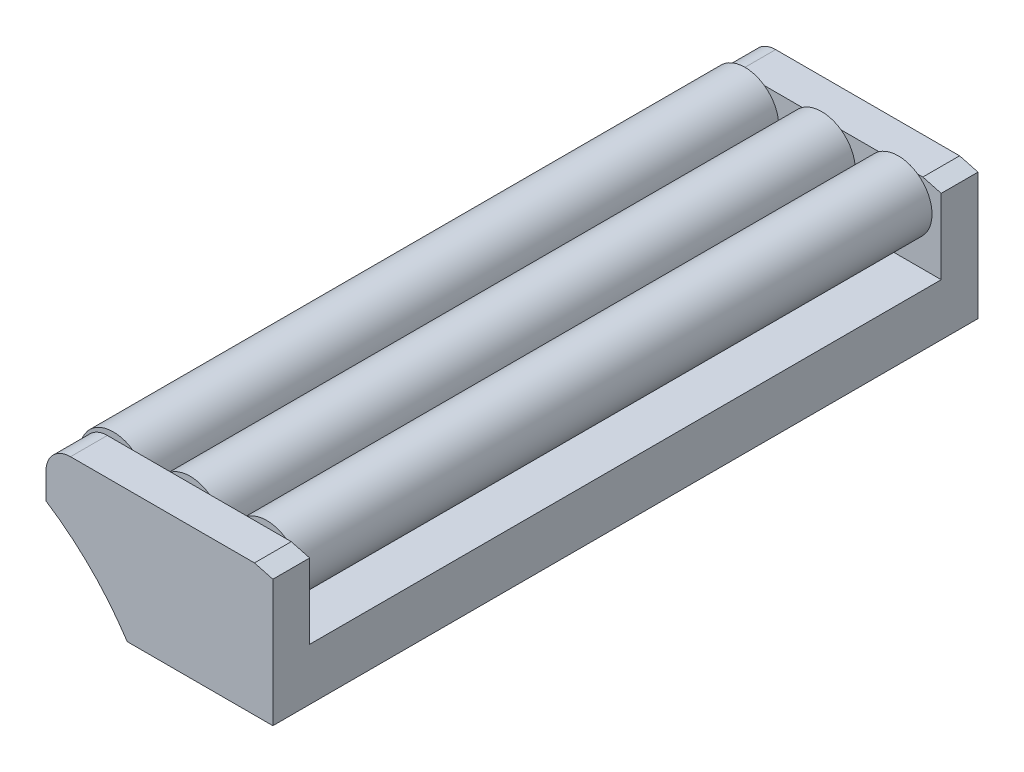
SolidWorks part; units mm, degrees
ref_plane "Frontale" through (0, 0, 0) normal (0, 0, 1) x (1, 0, 0)
ref_plane "Superiore" through (0, 0, 0) normal (0, 1, 0) x (1, 0, 0)
ref_plane "Destro" through (0, 0, 0) normal (1, 0, 0) x (0, 0, -1)
sketch "Schizzo1" plane through (0, 0, 0) normal (0, 0, 1) x (1, 0, 0)
  line L1 (0, 0) -> (37, 0)
  line L2 (0, 0) -> (0, 21.5)
  line L3 (0, 21.5) -> (37, 21.5)
  line L4 (37, 0) -> (37, 21.5)
  dimension "D1" = 37
  dimension "D2" = 21.5
extrude "Estrusione1" add sketch "Schizzo1" along normal blind 115
sketch "Schizzo6" plane through (37, 0, 0) normal (1, 0, 0) x (0, 0, -1)
  line L1 (-115, 0) -> (-115, 21.5) construction
  line L2 (-115, 0) -> (0, 0) construction
  line L9 (-109, 32.1395) -> (-6, 32.1395)
  line L10 (-109, 32.1395) -> (-109, 8.5)
  line L11 (-109, 8.5) -> (-6, 8.5)
  line L12 (-6, 32.1395) -> (-6, 8.5)
  line L13 (-317.5773, 8.5) -> (13.8875, 8.5) construction
  dimension "D1" = 6
  dimension "D2" = 8.5
  dimension "D5" = 6
extrude "Taglio-Estrusione4" cut sketch "Schizzo6" against normal blind 84
sketch "Schizzo7" plane through (0, 0, 6) normal (0, 0, 1) x (1, 0, 0)
  line L0 (-1.4369, 17) -> (39.1559, 17) construction
  line L1 (0, 21.5) -> (0, 0) construction
  line L4 (-9.1685, 22.5) -> (40.6482, 22.5) construction
  circle A0 centre (5, 17) radius 5.5
  circle A1 centre (17.5, 17) radius 5.5
  circle A2 centre (30, 17) radius 5.5
  dimension "D1" = 11
  dimension "D2" = 11
  dimension "D3" = 11
  dimension "D4" = 12.5
  dimension "D5" = 12.5
  dimension "D6" = 5
  dimension "D7" = 17
extrude "Estrusione4" add sketch "Schizzo7" along normal up to surface (103 mm away) up to face at (18.5, 15, 109)
chamfer "Smusso1" distance 3 angle 15 2 edges at (37, 21.5, 3) (37, 21.5, 112) first distance on face at (17.9, 21.5, 4.8) first distance on face at (17.9, 21.5, 110.2)
fillet "Raccordo1" radius 4 2 edges at (0, 21.5, 112) (0, 21.5, 3)
sketch "Schizzo8" plane through (0, 0, 115) normal (0, 0, 1) x (1, 0, 0)
  line L0 (13, 34.4094) -> (13, -14.7843) construction
  line L1 (-11.3793, 13) -> (48.784, 13) construction
  line L2 (0, 0) -> (37, 0) construction
  line L3 (13, 13) -> (-36.0671, -36.0671) construction
  circle A0 centre (-24.5, -24.5) radius 45
  dimension "D4" = 90
  dimension "D1" = 13
  dimension "D2" = 13
  dimension "D3" = 45
  dimension "D5" = 37.5
extrude "Taglio-Estrusione5" cut sketch "Schizzo8" against normal through all
sketch "Schizzo9" plane through (0, 0, 0) normal (0, -1, 0) x (1, 0, 0)
  line L0 (13.2459, 115) -> (37, 115) construction
  line L1 (23, 127.0005) -> (23, -20.4205) construction
  line L4 (37, 115) -> (37, 0) construction
  circle A0 centre (23, 105.5) radius 3
  circle A1 centre (23, 9.5) radius 3
  dimension "D1" = 6
  dimension "D2" = 6
  dimension "D3" = 96
  dimension "D4" = 9.5
  dimension "D5" = 14
extrude "Taglio-Estrusione6" cut sketch "Schizzo9" against normal up to surface (8.5 mm away) up to face at (21.5471, 8.5, 57.5)
